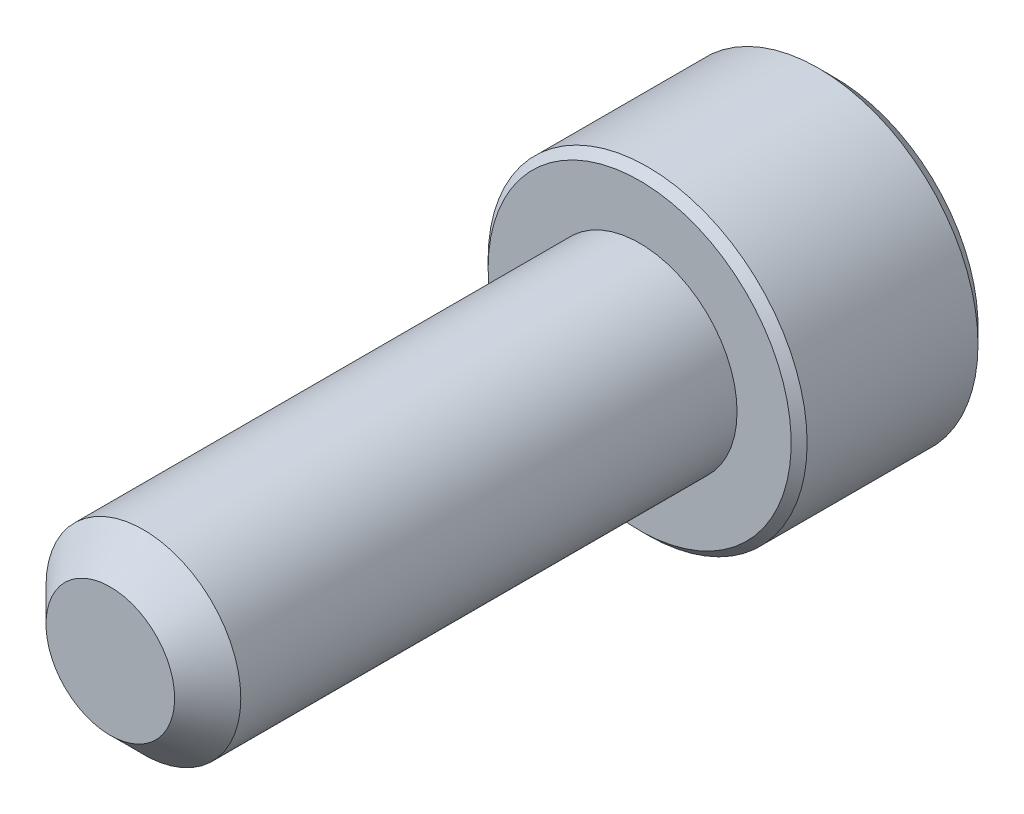
SolidWorks part; units mm, degrees
material "AISI 304"
ref_plane "Front Plane" through (0, 0, 0) normal (0, 0, 1) x (1, 0, 0)
ref_plane "Top Plane" through (0, 0, 0) normal (0, 1, 0) x (1, 0, 0)
ref_plane "Right Plane" through (0, 0, 0) normal (1, 0, 0) x (0, 0, -1)
sketch "Sketch0" plane through (0, 0, 0) normal (1, 0, 0) x (0, 0, -1)
  line L0 (0, 0) -> (9.525, 0) construction
  point P2 (13.0302, 0)
  point P4 (0, 0)
  dimension "D1" = 9.525
  dimension "D2" = 3.5052
  dimension "Min Thread" = 0
sketch "Sketch1" plane through (0, 0, 0) normal (0, 0, 1) x (1, 0, 0)
  circle A0 centre (0, 0) radius 1.7526
  dimension "OD" = 3.5052
extrude "Extrude1" add sketch "Sketch1" against normal blind 9.525
sketch "Sketch2" plane through (0, 0, 0) normal (0, 0, 1) x (1, 0, 0)
  circle A0 centre (0, 0) radius 1.7526 construction
  circle A1 centre (0, 0) radius 1.7526
curve "Helix/Spiral1" pitch 0.7937 height 10.3188 turns 13 parameters "pitch"=0.7937
chamfer "Chamfer3" distance 0.5953 angle 45 1 edges at (1.7526, 0, 0)
sketch "Sketch3" plane through (0, 0, 0) normal (1, 0, 0) x (0, 0, -1)
  line L0 (-0.6945, 1.7526) -> (-0.3969, 1.237)
  line L1 (-0.3969, 1.237) -> (-0.2977, 1.237)
  line L2 (-0.2977, 1.237) -> (0, 1.7526)
  line L3 (-0.6945, 1.7526) -> (0, 1.7526)
  line L4 (-0.3473, 1.7526) -> (-0.3473, 1.237) construction
  line L5 (-0.5457, 1.4948) -> (-0.1488, 1.4948) construction
  line L6 (0, 1.7526) -> (0, -1.7526) construction
  dimension "D1" = 0.0992
  dimension "D2" = 0.3969
  dimension "D3" = 60
sweep "Cut-Sweep1" [suppressed] cut profiles "Sketch3" path "Helix/Spiral1"
sketch "Sketch5" [suppressed] plane through (0, 0, 0) normal (1, 0, 0) x (0, 0, -1)
  line L0 (9.525, -1.2539) -> (9.525, 1.2505) construction
  line L1 (9.525, 1.7526) -> (0, 1.7526)
  line L2 (9.525, 1.7526) -> (9.525, 0)
  line L3 (9.525, 0) -> (-0.6379, 0)
  line L4 (0, 0) -> (9.525, 0) construction
  line L5 (0, 1.7526) -> (-0.6379, 0)
  line L6 (0, 0) -> (12.065, 0) construction
  dimension "D1" = 70
  dimension "D3" = 2.54
revolve "partially thread" [suppressed] add sketch "Sketch5" angle 360 about L6
sketch "Sketch6" plane through (0, 0, -9.525) normal (0, 0, -1) x (-1, 0, 0)
  circle A0 centre (0, 0) radius 2.8702
  dimension "head dia" = 5.7404
extrude "Extrude2" add sketch "Sketch6" along normal blind 3.5052
sketch "Sketch7" plane through (0, 0, -13.0302) normal (0, 0, -1) x (-1, 0, 0)
  line L1 (0, 1.604) -> (-1.3891, 0.802)
  line L2 (-1.3891, 0.802) -> (-1.3891, -0.802)
  line L3 (-1.3891, -0.802) -> (0, -1.604)
  line L4 (0, -1.604) -> (1.3891, -0.802)
  line L5 (1.3891, -0.802) -> (1.3891, 0.802)
  line L6 (1.3891, 0.802) -> (0, 1.604)
  circle A0 centre (0, 0) radius 1.3891 construction
  dimension "hex dia" = 2.7781
extrude "Cut-Extrude1" cut sketch "Sketch7" against normal blind 2.0836
sketch "Sketch8" plane through (0, 0, -13.0302) normal (0, 0, -1) x (-1, 0, 0)
  circle A0 centre (0, 0) radius 1.604
extrude "Cut-Extrude2" cut sketch "Sketch8" against normal through all draft 45
chamfer "Chamfer1" distance 0.287 angle 45 1 edges at (-2.8702, 0, -13.0302)
chamfer "Chamfer2" distance 0.1435 angle 45 1 edges at (-2.8702, 0, -9.525)
sketch "Sketch9" plane through (0, 0, 0) normal (1, 0, 0) x (0, 0, -1)
  line L0 (0, 1.7526) -> (0, -1.7526) construction
  line L1 (1.9844, 1.7526) -> (1.9844, -1.7526) construction
  line L2 (13.0302, 2.8702) -> (13.0302, -2.8702) construction
  line L3 (9.525, 2.8702) -> (9.525, -2.8702) construction
  line L4 (9.525, 2.7267) -> (9.525, -2.7267) construction
  line L5 (13.0302, -2.5832) -> (13.0302, 2.5832) construction
  line L6 (9.525, -2.8702) -> (9.525, 2.8702) construction
  line L7 (0, 1.1573) -> (0, -1.1573) construction
  line L8 (-0.6945, 1.7526) -> (0, 1.7526) construction
  line L9 (1.9844, 0) -> (0, 0) construction
  dimension "D1" = 1.9844
equation "\"D3@Helix/Spiral1\" = \"screw length@Extrude1\"+\"pitch@Helix/Spiral1\""
equation "\"D1@Sketch3\" = \"pitch@Helix/Spiral1\"*.125"
equation "\"D2@Sketch3\" = \"pitch@Helix/Spiral1\"*.5"
equation "\"D1@Cut-Extrude1\" = \"hex dia@Sketch7\"*.75"
equation "\"D1@Chamfer1\" = \"head dia@Sketch6\"*.05"
equation "\"D1@Sketch9\" = \"pitch@Helix/Spiral1\"*2.50"
equation "\"D1@Chamfer2\" = \"D1@Chamfer1\"/2"
equation "\"D1@Chamfer3\" = \"pitch@Helix/Spiral1\"*.750"
equation "\"D1@Sketch0\" = \"screw length@Extrude1\""
equation "\"D2@Sketch0\" = \"head depth@Extrude2\""
